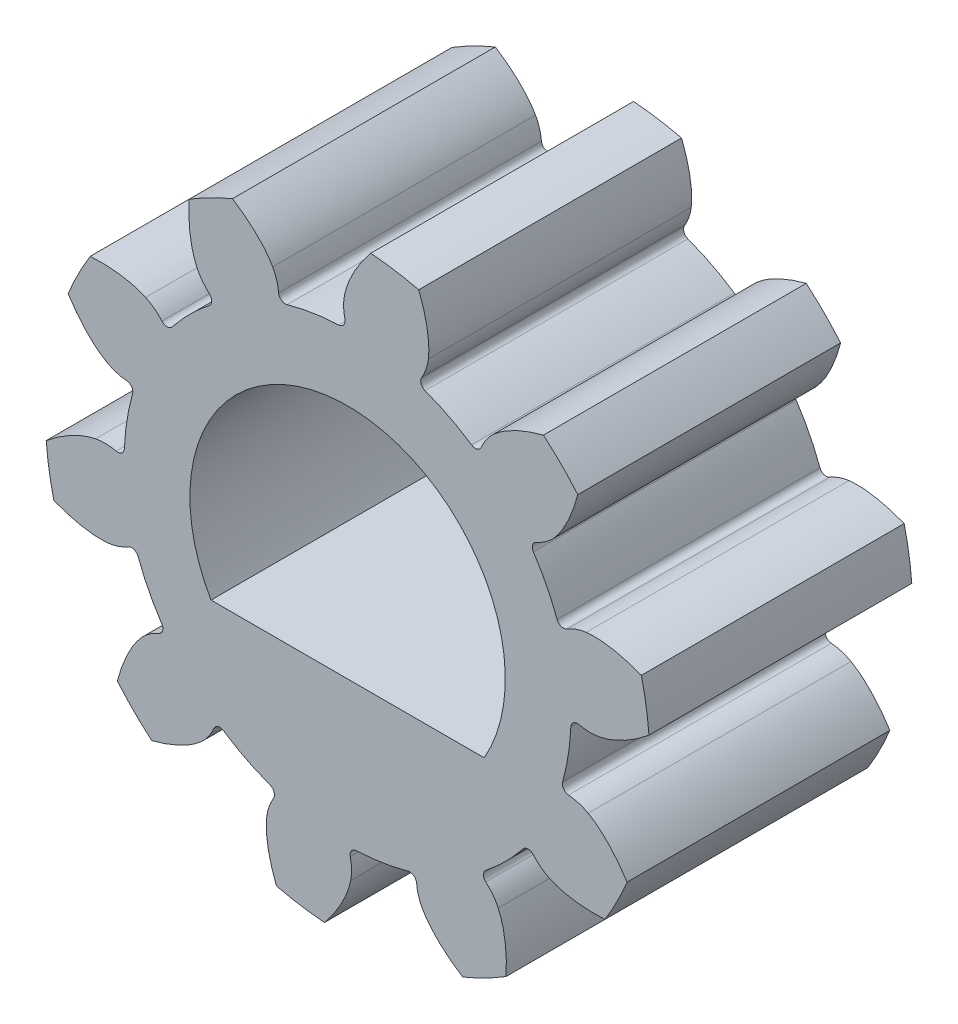
SolidWorks part; units mm, degrees
ref_plane "Front Plane" through (0, 0, 0) normal (0, 0, 1) x (1, 0, 0)
ref_plane "Top Plane" through (0, 0, 0) normal (0, 1, 0) x (1, 0, 0)
ref_plane "Right Plane" through (0, 0, 0) normal (1, 0, 0) x (0, 0, -1)
ref_axis "Axis1" through (0, 0, -2.75) along (0, 0, 1)
sketch "Sketch1" plane through (0, 0, 0) normal (0, 0, 1) x (1, 0, 0)
  circle A0 centre (0, 0) radius 4.25 construction
  circle A1 centre (0, 0) radius 5.75 construction
  circle A2 centre (0, 0) radius 5 construction
  circle A3 centre (0, 0) radius 3.25 construction
  dimension "D1" = 8.5
  dimension "D2" = 10
  dimension "D3" = 11.5
  dimension "D4" = 1
sketch "Sketch2" plane through (0, 0, 0) normal (0, 1, 0) x (1, 0, 0)
  line L0 (0, 2.5) -> (0, -2.5) construction
  point P3 (0, 0)
  dimension "D1" = 5
sketch "Sketch3" plane through (0, 0, 0) normal (0, 0, 1) x (1, 0, 0)
  circle A0 centre (0, 0) radius 3.25 construction
  circle A1 centre (0, 0) radius 4.25 construction
  circle A2 centre (0, 0) radius 3.25
  circle A3 centre (0, 0) radius 4.25
extrude "Boss-Extrude1" add sketch "Sketch3" along normal up to vertex (2.5 mm away) and the other way up to vertex (2.5 mm away) up to point (0, 0, 2.5) other way up to point (0, 0, -2.5)
sketch "Sketch4" plane through (0, 0, 0) normal (0, 0, 1) x (1, 0, 0)
  line L0 (-1.7101, -5) -> (0, -5) construction
  line L1 (0, -5) -> (1.7101, -5) construction
  line L2 (-1.607, -4.4151) -> (0, -5) construction
  line L3 (0, -5) -> (1.607, -5.5849) construction
  line L4 (-1.607, -4.4151) -> (0, 0) construction
  line L5 (0, 0) -> (-2.2995, -4.0973) construction
  line L6 (-2.2995, -4.0973) -> (-0.1437, -5.3072) construction
  line L7 (-4.3092, -1.8726) -> (-3.9498, -2.5445) construction
  line L8 (-3.4866, -3.1495) -> (-3.9498, -2.5445) construction
  line L9 (-3.4866, -3.1495) -> (-2.9316, -3.6717) construction
  line L10 (-2.9316, -3.6717) -> (-2.2995, -4.0973) construction
  line L11 (-2.2995, -4.0973) -> (-1.607, -4.4151) construction
  line L12 (-2.9316, -3.6717) -> (-0.4043, -5.6896) construction
  line L13 (-3.4866, -3.1495) -> (-0.8078, -6.1149) construction
  line L14 (-3.9498, -2.5445) -> (-1.373, -6.5445) construction
  line L15 (-4.3092, -1.8726) -> (-2.1091, -6.9353) construction
  line L16 (-4.5552, -1.1514) -> (-3.0157, -7.2419) construction
  line L17 (-4.5552, -1.1514) -> (-4.3092, -1.8726) construction
  line L18 (-1.607, -4.4151) -> (-0.8721, -4.6168) construction
  line L19 (-0.8721, -4.6168) -> (0.0595, -4.7928) construction
  line L20 (0, 0) -> (0, -3.25) construction
  line L21 (0, 0) -> (-1.5643, -9.8769) construction
  line L22 (0.0021, -4.25) -> (-1.3153, -4.0413)
  arc A0 (-1.607, -4.4151) -> (-2.2995, -4.0973) centre (0, 0) cw construction
  arc A1 (-2.2995, -4.0973) -> (-2.9316, -3.6717) centre (0, 0) cw construction
  circle A2 centre (0, 0) radius 4.6985 construction
  circle A3 centre (0, 0) radius 5 construction
  arc A4 (-2.9316, -3.6717) -> (-3.4866, -3.1495) centre (0, 0) cw construction
  arc A5 (-3.4866, -3.1495) -> (-3.9498, -2.5445) centre (0, 0) cw construction
  arc A6 (-3.9498, -2.5445) -> (-4.3092, -1.8726) centre (0, 0) cw construction
  arc A7 (-4.3092, -1.8726) -> (-4.5552, -1.1514) centre (0, 0) cw construction
  arc A8 (-1.607, -4.4151) -> (-0.8721, -4.6168) centre (0, 0) ccw construction
  arc A9 (0.0595, -4.7928) -> (0.0021, -4.25) centre (-0.8721, -4.6168) ccw
  circle A10 centre (0, 0) radius 3.25 construction
  arc A11 (-1.5376, -4.5398) -> (-1.3153, -4.0413) centre (-0.5972, -4.6604) cw
  arc A12 (-1.3534, -5.5884) -> (-0.4397, -5.7332) centre (0, 0) ccw
  circle A13 centre (0, 0) radius 4.25 construction
  circle A14 centre (0, 0) radius 5.75 construction
  spline S0 degree 3 poles (-3.0157, -7.2419) (-2.4377, -7.096) (-1.6527, -6.7769) (-0.8271, -6.1554) (-0.4192, -5.7305) (-0.1144, -5.2889) (0.0216, -4.9745) (0.0595, -4.7928) knots 0 0 0 0 0.43627 0.609238 0.752095 0.86484 1 1 1 1
  spline S1 degree 3 poles (0.6303, -7.8194) (0.1256, -7.502) (-0.5224, -6.9559) (-1.1155, -6.1097) (-1.3721, -5.5796) (-1.5256, -5.0654) (-1.5577, -4.7244) (-1.5376, -4.5398) knots 0 0 0 0 0.43627 0.609238 0.752095 0.86484 1 1 1 1
  point P23 (0, -4.6985)
  point P41 (-0.6566, -4.1457)
  dimension "D1" = 1.7101
  dimension "D2" = 20
  dimension "D3" = 0.762
  dimension "D4" = 2.4721
  dimension "D5" = 3.2341
  dimension "D6" = 3.9961
  dimension "D7" = 4.7581
  dimension "D8" = 5.5201
  dimension "D9" = 6.2821
  dimension "D10" = 0.762
  dimension "D11" = 0.9481
  dimension "D12" = 9
  dimension "D13" = 10
extrude "Boss-Extrude2" add sketch "Sketch4" along normal mid plane 5 contours S1 S0 A9 L22 A11 region at (-0.7702, -4.8629, 0)
fillet "Fillet1" radius 0.127 2 edges at (0.0021, -4.25, 0) (-1.3153, -4.0413, 0)
pattern_circular "CirPattern2" count 10 over 360 about axis through (0, 0, -2.5) along (0, 0, 1) of "Boss-Extrude2", "Fillet1" reverse direction yes
sketch "Sketch6" plane through (0, 0, 0) normal (0, 0, 1) x (1, 0, 0)
  circle A0 centre (0, 0) radius 3.25 construction
  circle A1 centre (0, 0) radius 3.25
  circle A2 centre (0, 0) radius 12.7
  dimension "D1" = 25.4
sketch "Sketch5" plane through (0, 0, 0) normal (0, 0, 1) x (1, 0, 0)
  line L0 (-2.5981, -1.5) -> (2.5981, -1.5)
  line L1 (0, -1.5) -> (0, 3) construction
  line L2 (3.25, 0) -> (4.25, 0) construction
  circle A2 centre (0, 0) radius 3
  circle A3 centre (0, 0) radius 3.75
  circle A4 centre (0, 0) radius 3.25 construction
  circle A5 centre (0, 0) radius 4.25 construction
  point P14 (3.75, 0)
  dimension "D1" = 6
  dimension "D2" = 4.5
extrude "Boss-Extrude3" add sketch "Sketch5" along normal mid plane 5 contours A2 | L0 A2 region at (0, -2.1151, 0) region at (-3.6439, 0, 0)
equation "\"Pitch_Diameter\"= \"Tooth Number\" * \"Tooth Pitch\""
equation "\"OD\"= \"Pitch_Diameter\" + \"Tooth Pitch\" * 1.5"
equation "\"Tooth Number\"= 10"
equation "\"Tooth Pitch\"= 1mm"
equation "\"ID\"= \"Pitch_Diameter\" - \"Tooth Pitch\" * 1.5"
equation "\"D2@Sketch1\"=\"Pitch_Diameter\""
equation "\"D3@Sketch1\"=\"OD\""
equation "\"D1@Sketch1\"=\"ID\""
equation "\"D4@Sketch1\"=\"Tooth Pitch\""
equation "\"Thicknes\" = 5mm"
equation "\"D1@Sketch2\"=\"Thicknes\""
equation "\"Contact_angle\"= 20"
equation "\"length\"= sin ( 20 ) * \"Pitch_Diameter\" / 2"
equation "\"D1@Sketch4\"= \"length\""
equation "\"D2@Sketch4\"=\"Contact_angle\""
equation "\"arbitrary\"=0.03"
equation "\"D3@Sketch4\"=\"arbitrary\""
equation "\"D4@Sketch4\"=\"arbitrary\"+\"length\""
equation "\"D5@Sketch4\"=\"arbitrary\"*2+\"length\""
equation "\"D6@Sketch4\"=\"arbitrary\"*3+\"length\""
equation "\"D7@Sketch4\"=\"arbitrary\"*4+\"length\""
equation "\"D8@Sketch4\"=\"length\"+\"arbitrary\"*5"
equation "\"D9@Sketch4\"=\"length\"+\"arbitrary\"*6"
equation "\"D10@Sketch4\"=\"arbitrary\""
equation "\"D11@Sketch4\"=\"length\"-\"arbitrary\""
equation "\"D12@Sketch4\"=360/\"Tooth Number\"/4"
equation "\"D13@Sketch4\"=\"Pitch_Diameter\""
equation "\"D1@Boss-Extrude2\"=\"Thicknes\""
equation "\"D1@CirPattern1\"=\"Tooth Number\""
equation "\"D1@Boss-Extrude3\"=\"Thicknes\""
equation "\"D1@Boss-Extrude4\"=\"Thicknes\""
equation "\"D1@Boss-Extrude5\"=\"Thicknes\""
equation "\"D1@CirPattern2\"=\"Tooth Number\""
equation "\"ID\" = \"Pitch_Diameter\""
equation "\"Thickness\"= 5mm"
